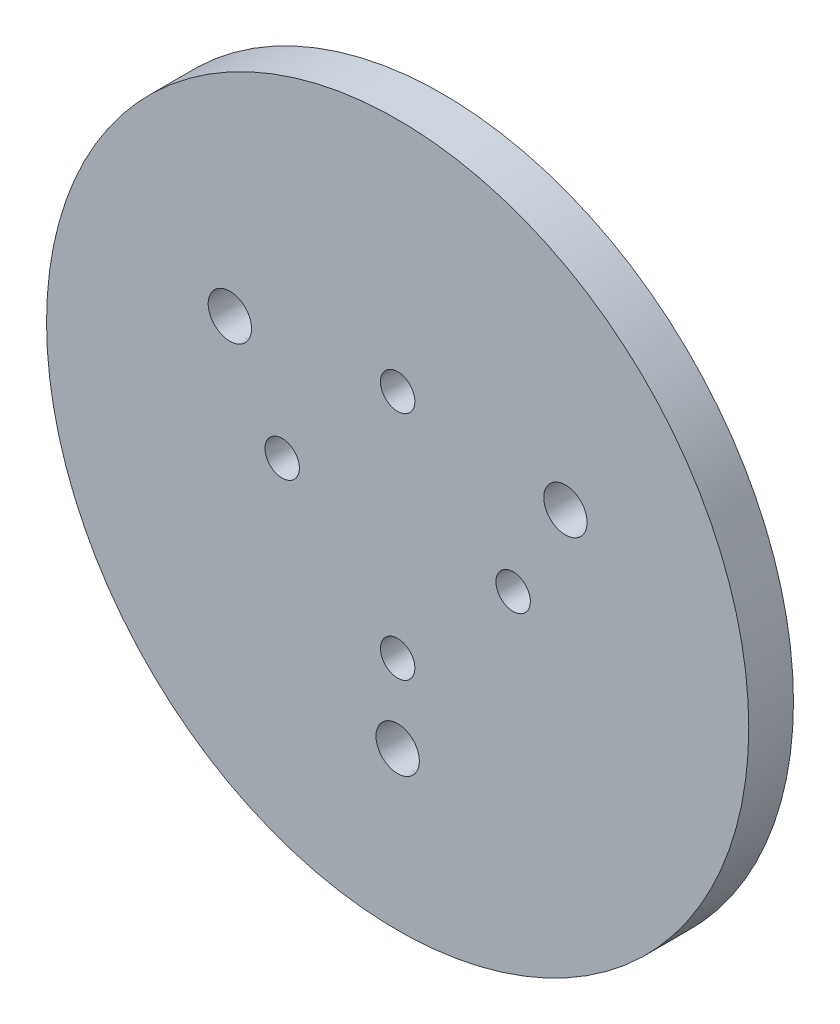
SolidWorks part; units mm, degrees
other "Markup1"
sketch "Sketch6" plane through (31.1257, -31.1257, 6.6) normal (0.5824, -0.4463, 0.6794) x (0.0162, 0.842, 0.5392)
ref_plane "Front Plane" through (0, 0, 0) normal (1, 0, 0) x (0, 1, 0)
ref_plane "Top Plane" through (0, 0, 0) normal (0, 0, 1) x (0, 1, 0)
ref_plane "Right Plane" through (0, 0, 0) normal (0, 1, 0) x (-1, 0, 0)
sketch "Sketch1" plane through (0, 0, 0) normal (0, 0, 1) x (0, 1, 0)
  circle A0 centre (0, 0) radius 47.125
  dimension "D1" = 94.25
extrude "Boss-Extrude1" add sketch "Sketch1" along normal blind 6 contours A0 region at (0, 0, 0)
sketch "Sketch2" plane through (0, 0, 6) normal (0, 0, -1) x (1, 0, 0)
  circle A0 centre (0, 0) radius 26 construction
  circle A1 centre (0, 26) radius 2.7
  circle A2 centre (22.5167, -13) radius 2.7
  circle A3 centre (-22.5167, -13) radius 2.7
  circle A4 centre (0, 0) radius 15.5 construction
  circle A5 centre (-15.5, 0) radius 2.1
  circle A11 centre (0, 15.5) radius 2.1
  circle A12 centre (15.5, 0) radius 2.1
  circle A13 centre (0, -15.5) radius 2.1
  dimension "D1" = 52
  dimension "D2" = 5.4
  dimension "D4" = 31
  dimension "D5" = 4.2
  dimension "D3" = 3
  dimension "D6" = 4
extrude "Cut-Extrude1" cut sketch "Sketch2" against normal through all draft 2 from surface draft outward yes starting at face at (47.125, 0, 0)
equation "\"D4@Sketch2\"=31"
equation "\"SunTeeth\"= 12"
equation "\"PlanetTeeth\" = 40"
equation "\"Module\" = 1"
equation "\"OrbitDiameter\"= \"SunTeeth\" * \"Module\" + \"PlanetTeeth\" * \"Module\""
equation "\"RingDiameter\"= ( \"SunTeeth\" + 2 * \"PlanetTeeth\" ) * \"Module\""
equation "\"BearingBore\" = 4"
equation "\"D1@Sketch2\"=\"OrbitDiameter\""
equation "\"D2@Sketch2\"=5.4"
equation "\"PressureAngle\" = 20deg"
equation "\"GearWidth\"=10"
equation "\"BearingDiameter\" = 13"
equation "\"ShaftDiameter\"= 6.5"
equation "\"D1@Sketch1\"=( \"SunTeeth\" + 2 * \"PlanetTeeth\" ) * \"Module\"+ 2.25*\"Module\""
